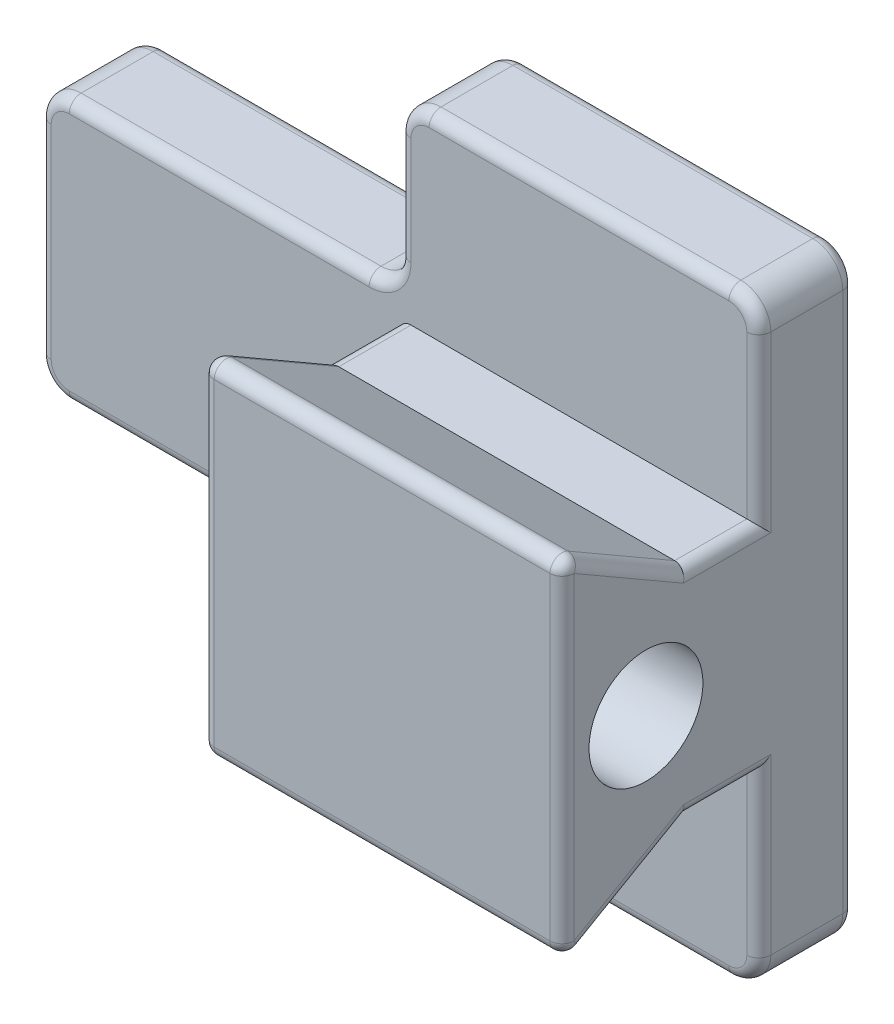
SolidWorks part; units mm, degrees
material "Polyetheretherketone (PEEK)"
ref_plane "Front Plane" through (0, 0, 0) normal (0, 0, 1) x (1, 0, 0)
ref_plane "Top Plane" through (0, 0, 0) normal (0, 1, 0) x (1, 0, 0)
ref_plane "Right Plane" through (0, 0, 0) normal (1, 0, 0) x (0, 0, -1)
sketch "Sketch1" plane through (0, 0, 0) normal (1, 0, 0) x (0, 0, -1)
  line L0 (0, -1.5) -> (0, 1.5)
  line L1 (0, 1.5) -> (1.0392, 0.9)
  line L2 (1.0392, -0.9) -> (1.6413, -0.9)
  line L3 (1.6413, 2.5) -> (2.4413, 2.5)
  line L4 (2.4413, 2.5) -> (2.4413, -2.5)
  line L5 (2.4413, -2.5) -> (1.6413, -2.5)
  line L6 (1.6413, -0.9) -> (1.6413, -2.5)
  line L7 (1.0392, -0.9) -> (0, -1.5)
  line L8 (1.0392, 0.9) -> (1.6413, 0.9)
  line L9 (1.6413, 0.9) -> (1.6413, 2.5)
  line L11 (2.4413, -1.1) -> (1.6413, -1.1)
  line L12 (2.4413, -1.1) -> (2.4413, 1.1)
  line L13 (2.4413, 1.1) -> (1.6413, 1.1)
  line L14 (1.6413, -1.1) -> (1.6413, 1.1)
  line L15 (2.4413, -1.1) -> (1.6413, 1.1) construction
  line L16 (2.4413, 1.1) -> (1.6413, -1.1) construction
  point P3 (0.7, 0)
  point P4 (0, 0)
  point P12 (2.4413, 0)
  point P13 (2.0413, 0)
  dimension "D1" = 3
  dimension "D2" = 60
  dimension "D3" = 60
  dimension "D4" = 5
  dimension "D5" = 0.8
  dimension "D6" = 0.6021
  dimension "D7" = 1.8
  dimension "D8" = 0
  dimension "D9" = 0.7
  dimension "D10" = 0
  dimension "D11" = 0
  dimension "D12" = 0
  dimension "D13" = 2.2
extrude "Boss-Extrude1" add sketch "Sketch1" along normal blind 3 contours L8 L1 L0 L7 L2 | L9 L6 L5 L4 L3 | L4 L11 L6 L5 | L13 L4 L3 L9 region at (0, 0, -0.738) region at (0, 0, -2.0413) region at (0, -1.8, -2.0413) region at (0, 1.8, -2.0413)
extrude "Boss-Extrude2" add sketch "Sketch1<4>" against normal blind 3 contours L14 L6 L11 L4 L13 L9 region at (0, 0, -2.0413)
sketch "Sketch1<4>" plane through (0, 0, 0) normal (1, 0, 0) x (0, 0, -1) same geometry as "Sketch1"
hole_wizard "M1.2x0.25 Tapped Hole1" positions "Sketch2" profile "Sketch3" tap size "M1.2x0.25" standard "ISO" end condition through all
sketch "Sketch2" plane through (0, 0, 0) normal (-1, 0, 0) x (0, 0, 1)
  line L0 (0, -1.5) -> (0, 1.5) construction
  point P0 (-0.7, 0)
  point P6 (0, 0)
  point P7 (-0.7, -0.283)
  dimension "D1" = 0.7
  dimension "D2" = 0
sketch "Sketch3" plane through (0, 0, -0.7) normal (0, 1, 0) x (0, 0, 1)
  line L0 (0, 0) -> (0, 3)
  line L1 (0, 3) -> (0.475, 3)
  line L2 (0.475, 3) -> (0.475, 0)
  line L5 (0.475, 0) -> (0, 0)
  line L11 (0, -6.35) -> (0, 107.95) construction
  dimension "Thru Tap Drill Dia." = 0.95
  dimension "Thru Tap Drill Depth" = 3
cosmetic thread "Hole Thread1" parameters "D2"=1.2
fillet "Fillet1" radius 0.25 8 edges at (0, -1.1, -2.0413) (0, -2.5, -2.0413) (3, -2.5, -2.0413) (3, 2.5, -2.0413) (0, 2.5, -2.0413) (0, 1.1, -2.0413) (-3, -1.1, -2.0413) (-3, 1.1, -2.0413)
fillet "Fillet2" radius 0.1 43 edges at (1.5, 1.5, 0) (1.5, -1.5, 0) (0, 0, 0) (0, 1.2, -0.5196) (0, 0.9, -1.3403) (0, -1.2, -0.5196) (0, -0.9, -1.3403) (3, -1.2, -0.5196) (3, 0, 0) (3, 1.2, -0.5196) (3, -0.9, -1.3403) (3, 0.9, -1.3403) (2.9268, 2.4268, -2.4413) (3, 0, -2.4413) (2.9268, -2.4268, -2.4413) (1.5, 2.5, -2.4413) (0.0732, 2.4268, -2.4413) (0, 1.8, -2.4413) (1.5, -2.5, -2.4413) (0.0732, -2.4268, -2.4413) (-0.0732, -1.1732, -2.4413) (-1.5, -1.1, -2.4413) (-0.0732, 1.1732, -2.4413) (-1.5, 1.1, -2.4413) (-2.9268, 1.0268, -2.4413) (-2.9268, -1.0268, -2.4413) (-3, 0, -2.4413) (3, 1.575, -1.6413) (3, -1.575, -1.6413) (2.9268, -2.4268, -1.6413) (1.5, -2.5, -1.6413) (0.0732, -2.4268, -1.6413) (-0.0732, -1.1732, -1.6413) (0, 1.8, -1.6413) (2.9268, 2.4268, -1.6413) (1.5, 2.5, -1.6413) (0.0732, 2.4268, -1.6413) (-0.0732, 1.1732, -1.6413) (-1.5, 1.1, -1.6413) (-2.9268, 1.0268, -1.6413) (-3, 0, -1.6413) (-2.9268, -1.0268, -1.6413) (-1.5, -1.1, -1.6413)
